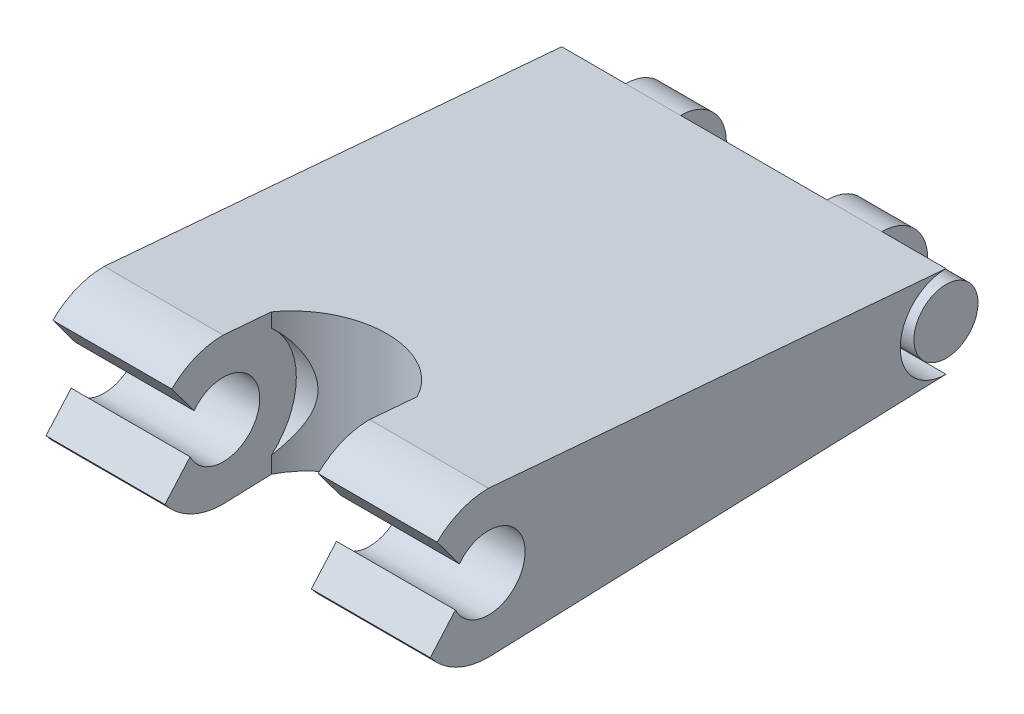
SolidWorks part; units mm, degrees
ref_plane "Front Plane" through (0, 0, 0) normal (0, 0, 1) x (1, 0, 0)
ref_plane "Top Plane" through (0, 0, 0) normal (0, 1, 0) x (1, 0, 0)
ref_plane "Right Plane" through (0, 0, 0) normal (1, 0, 0) x (0, 0, -1)
sketch "Sketch1" plane through (0, 0, 0) normal (1, 0, 0) x (0, 0, -1)
  line L0 (0, 8) -> (50, 3.7902)
  line L1 (50, -6.2098) -> (0, -8)
  circle A0 centre (0, 0) radius 8
  circle A1 centre (0, 0) radius 4
  circle A2 centre (50, -1.2098) radius 5
  circle A3 centre (50, -1.2098) radius 3.5
  dimension "D1" = 16
  dimension "D2" = 8
  dimension "D3" = 10
  dimension "D4" = 7
  dimension "D5" = 50
extrude "Boss-Extrude1" add sketch "Sketch1" along normal mid plane 42 contours A2 L0 A0 L1 | L0 A0 L1 A1 | A3 | A2 A3 region at (0, 7.7182, -0.6498) region at (0, -0.6178, -25.0448) region at (0, 2.2258, -53.4355) region at (0, -1.2098, -50)
extrude "Cut-Extrude2" cut sketch "Sketch1<4>" against normal mid plane 16 contours L0 A0 L1 A1 region at (0, 7.7182, -0.6498)
sketch "Sketch1<4>" plane through (0, 0, 0) normal (1, 0, 0) x (0, 0, -1) same geometry as "Sketch1"
extrude "Cut-Extrude3" cut sketch "Sketch1<5>" against normal mid plane 16 contours A2 A3 region at (0, 2.2258, -53.4355)
sketch "Sketch1<5>" plane through (0, 0, 0) normal (1, 0, 0) x (0, 0, -1) same geometry as "Sketch1"
extrude "Cut-Extrude4" cut sketch "Sketch1<6>" against normal blind 7 from offset 21 contours A2 A3 region at (0, 2.2258, -53.4355)
sketch "Sketch1<6>" plane through (0, 0, 0) normal (1, 0, 0) x (0, 0, -1) same geometry as "Sketch1"
mirror "Mirror1" about plane through (0, 0, 0) normal (1, 0, 0) of "Cut-Extrude4"
sketch "Sketch3" plane through (0, 0, 0) normal (0, 1, 0) x (1, 0, 0)
  line L0 (-8, 5.2722) -> (-8, -3.421)
  line L2 (-8, -3.421) -> (8, -3.421)
  line L4 (8, -3.421) -> (8, 5.2081)
  line L6 (8, 0) -> (8, -8) construction
  line L7 (-8, -8) -> (-8, 0) construction
  arc A0 (8, 5.2081) -> (-8, 5.2722) centre (-0.018, 0.7358) ccw
  dimension "D2" = 9.181
  dimension "D1" = 0.736
extrude "Cut-Extrude5" cut sketch "Sketch3" against normal mid plane 20
sketch "Sketch4" plane through (21, 0, 0) normal (1, 0, 0) x (0, 0, -1)
  line L2 (50, 3.7902) -> (0, 8)
  line L3 (0, -8) -> (50, -6.2098)
  line L6 (-5.6127, 5.7007) -> (-3.1794, 2.4272)
  line L7 (-6.3593, -4.8538) -> (-3.6133, -1.7158)
  arc A2 (50, 3.7902) -> (50, -6.2098) centre (50, -1.2098) ccw
  arc A3 (0, 8) -> (0, -8) centre (0, 0) ccw
  arc A4 (50, 3.7902) -> (50, -6.2098) centre (50, -1.2098) ccw
  circle A6 centre (0, 0) radius 4 construction
  arc A7 (-3.1794, 2.4272) -> (-3.6133, -1.7158) centre (0, 0) ccw
  arc A8 (0, 8) -> (0, -8) centre (0, 0) ccw construction
  arc A9 (-5.6127, 5.7007) -> (-6.3593, -4.8538) centre (0, 0) ccw
  point P0 (-5.6127, 5.7007)
  dimension "D1" = 0
extrude "Cut-Extrude6" cut sketch "Sketch4" against normal up to surface (42 mm away) contours L6 A7 L7 A9 up to face at (-21, 0, -4)
